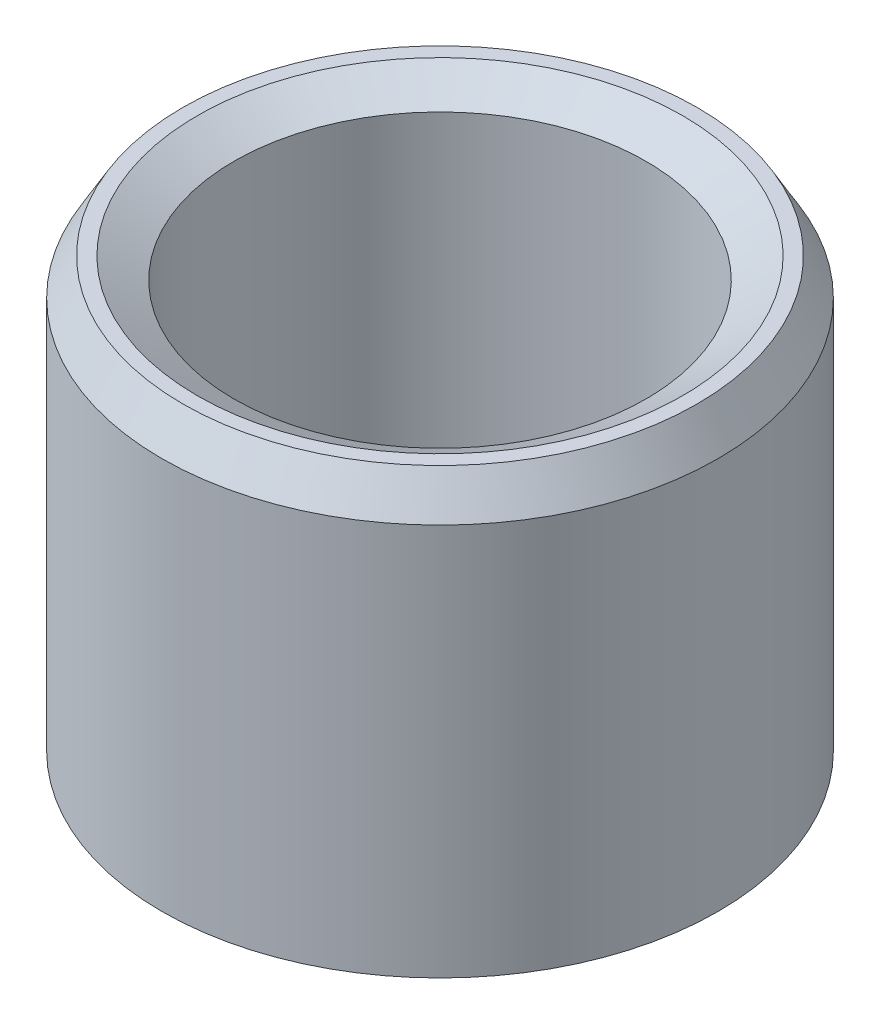
SolidWorks part; units mm, degrees
ref_plane "Front Plane" through (0, 0, 0) normal (0, 0, 1) x (1, 0, 0)
ref_plane "Top Plane" through (0, 0, 0) normal (0, 1, 0) x (1, 0, 0)
ref_plane "Right Plane" through (0, 0, 0) normal (1, 0, 0) x (0, 0, -1)
sketch "Sketch1" plane through (0, 0, 0) normal (0, 1, 0) x (1, 0, 0)
  circle A0 centre (0, 0) radius 10
  dimension "SLEEVE_OD" = 20
extrude "Boss-Extrude1" add sketch "Sketch1" along normal blind 16.178
sketch "Sketch2" plane through (0, 0, 0) normal (0, 1, 0) x (1, 0, 0)
  circle A0 centre (0, 0) radius 7.4051
  dimension "BORE_D" = 14.8103
extrude "Cut-Extrude1" cut sketch "Sketch2" along normal through all
chamfer "Chamfer1" distance 1.3176 angle 30 4 edges at (0, 16.178, 7.4051) (0, 0, 7.4051) (0, 0, 10) (0, 16.178, 10) first distance on face at (0, 16.178, 7.4051) first distance on face at (0, 0, 7.4051) first distance on face at (0, 16.178, 10)
